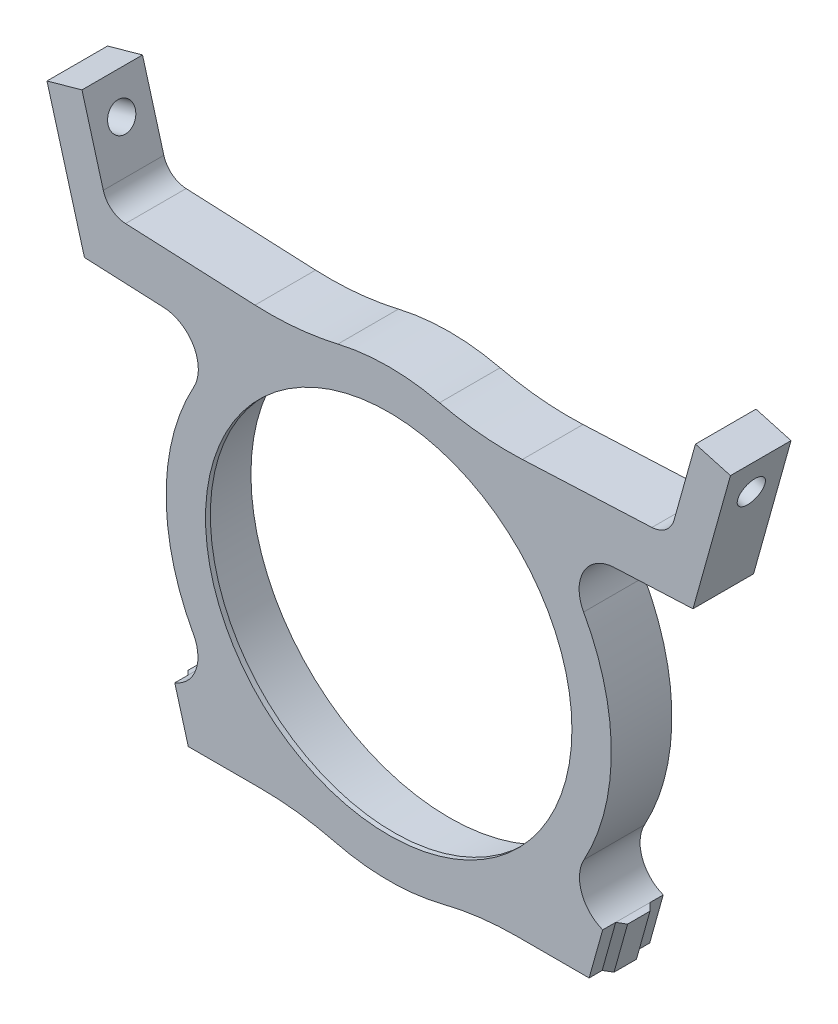
SolidWorks part; units mm, degrees
ref_plane "Ebene vorne" through (0, 0, 0) normal (0, 0, 1) x (1, 0, 0)
ref_plane "Ebene oben" through (0, 0, 0) normal (0, 1, 0) x (1, 0, 0)
ref_plane "Ebene rechts" through (0, 0, 0) normal (1, 0, 0) x (0, 0, -1)
sketch "Skizze1" plane through (0, 0, 0) normal (0, 0, 1) x (1, 0, 0)
  line L0 (-13.6359, -34.1266) -> (-33.0896, -34.1266)
  line L5 (-80.7379, 136.3891) -> (0, -152.5424) construction
  line L6 (-33.0896, -34.1266) -> (-35.3251, -26.1266)
  line L7 (-35.3251, -26.1266) -> (-25.845, -26.1266)
  line L8 (0, 0) -> (-26.219, 0) construction
  line L9 (0, 0) -> (0, -14.2745) construction
  line L10 (35.3251, -26.1266) -> (25.845, -26.1266)
  line L11 (33.0896, -34.1266) -> (35.3251, -26.1266)
  line L12 (13.6359, -34.1266) -> (33.0896, -34.1266)
  line L13 (-50.2356, 27.2324) -> (-25.845, 26.1266)
  line L14 (-13.6359, 34.1266) -> (-46.3466, 35.6096)
  line L15 (-50.2356, 27.2324) -> (-52.6564, 35.8957)
  line L16 (13.6359, 34.1266) -> (46.3466, 35.6096)
  line L17 (50.2356, 27.2324) -> (52.6564, 35.8957)
  line L18 (50.2356, 27.2324) -> (25.845, 26.1266)
  line L19 (80.7379, 136.3891) -> (0, -152.5424) construction
  line L20 (52.6564, 35.8957) -> (56.4242, 49.3792)
  line L21 (56.4242, 49.3792) -> (50.6456, 50.9939)
  line L22 (50.6456, 50.9939) -> (46.3466, 35.6096)
  line L23 (-52.6564, 35.8957) -> (-56.4242, 49.3792)
  line L24 (-56.4242, 49.3792) -> (-50.6456, 50.9939)
  line L25 (-50.6456, 50.9939) -> (-46.3466, 35.6096)
  circle A0 centre (0, 0) radius 32.75
  arc A1 (-13.6359, -34.1266) -> (13.6359, -34.1266) centre (0, 0) ccw
  arc A2 (-25.845, 26.1266) -> (-25.845, -26.1266) centre (0, 0) ccw
  arc A3 (25.845, -26.1266) -> (25.845, 26.1266) centre (0, 0) ccw
  arc A4 (13.6359, 34.1266) -> (-13.6359, 34.1266) centre (0, 0) ccw
  dimension "D1" = 65.5
  dimension "D2" = 4
  dimension "D3" = 8
  dimension "D4" = 14
  dimension "D5" = 6
extrude "Aufsatz-Linear austragen1" add sketch "Skizze1" along normal blind 10
sketch "Skizze2" plane through (0, 0, 10) normal (0, 0, 1) x (1, 0, 0)
  circle A0 centre (0, 0) radius 30.25
  circle A1 centre (0, 0) radius 32.75 construction
  circle A2 centre (0, 0) radius 32.75
  dimension "D1" = 2.5
extrude "Aufsatz-Linear austragen2" add sketch "Skizze2" against normal blind 0.8
sketch "Skizze5" plane through (33.7599, -9.4337, 0) normal (-0.9631, 0.2691, 0) x (0, 0, 1)
  line L0 (5, 62.7426) -> (5, 46.7689) construction
  line L1 (10, 62.7426) -> (0, 62.7426) construction
  line L2 (10, 46.7689) -> (0, 46.7689) construction
  circle A0 centre (5, 56.9498) radius 2.25
  dimension "D1" = 4.5
extrude "Schnitt-Linear austragen1" cut sketch "Skizze5" against normal blind 10
mirror "Spiegeln1" about plane through (0, 0, 0) normal (1, 0, 0) of "Schnitt-Linear austragen1"
fillet "Verrundung1" radius 50 4 edges at (-13.6359, 34.1266, 5) (13.6359, 34.1266, 5) (-13.6359, -34.1266, 5) (13.6359, -34.1266, 5)
fillet "Verrundung2" radius 6 4 edges at (-25.845, -26.1266, 5) (25.845, -26.1266, 5) (25.845, 26.1266, 5) (-25.845, 26.1266, 5)
fillet "Verrundung3" radius 4 2 edges at (46.3466, 35.6096, 5) (-46.3466, 35.6096, 5)
ref_plane "Ebene1" through (6.4489, -23.0781, 0) normal (-0.2691, 0.9631, 0) x (0, 0, -1)
sketch "Skizze6" plane through (6.4489, -23.0781, 0) normal (-0.2691, 0.9631, 0) x (0, 0, -1)
  line L0 (-5, 41.0532) -> (-5, 46.0217) construction
  line L1 (-10, 41.0532) -> (0, 41.0532) construction
  line L2 (-7.85, 41.0532) -> (-6.85, 42.0532)
  line L3 (-6.85, 42.0532) -> (-3.15, 42.0532)
  line L4 (-2.15, 41.0532) -> (-3.15, 42.0532)
  line L5 (-2.15, 41.0532) -> (-7.85, 41.0532)
  point P9 (-5, 42.0532)
  dimension "D1" = 45
  dimension "D2" = 5.7
  dimension "D3" = 1
extrude "Aufsatz-Linear austragen3" add sketch "Skizze6" along normal up to vertex (8.3065 mm away) up to point (-35.3251, -26.1266, 10)
mirror "Spiegeln2" about plane through (0, 0, 0) normal (1, 0, 0) of "Aufsatz-Linear austragen3"
